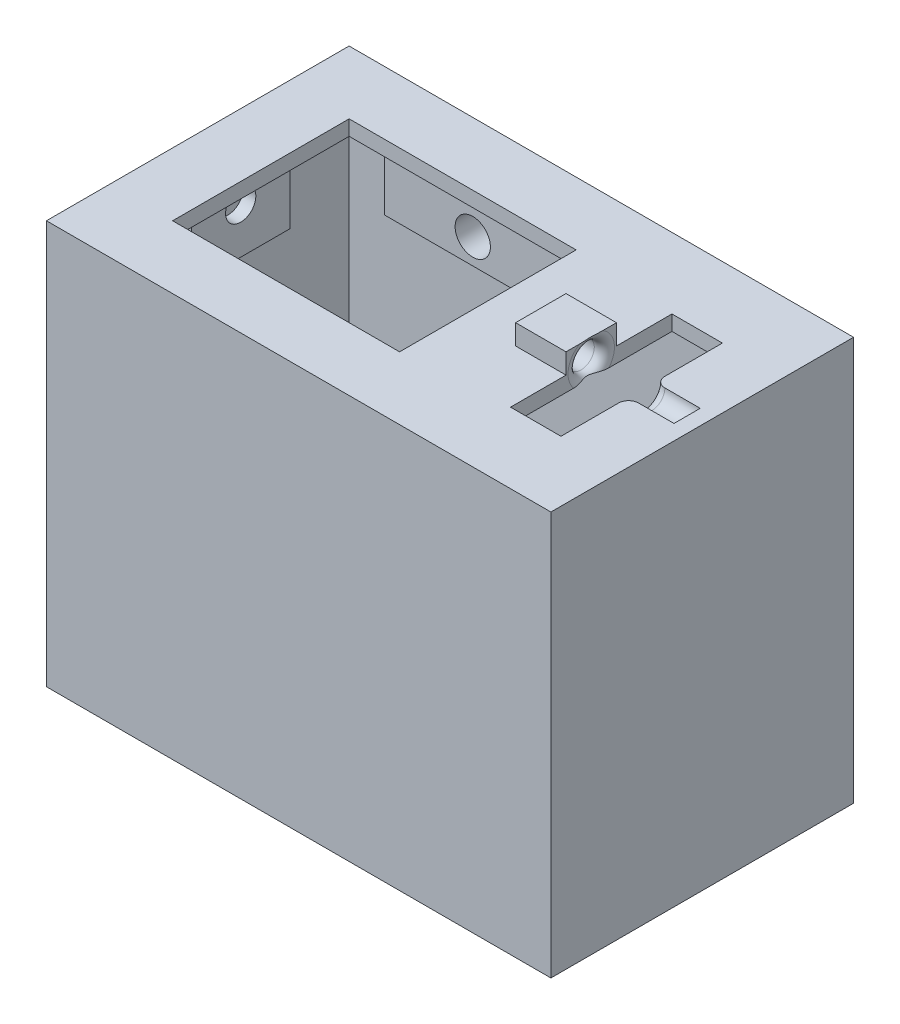
SolidWorks part; units mm, degrees
ref_plane "Front Plane" through (0, 0, 0) normal (0, 0, 1) x (1, 0, 0)
ref_plane "Top Plane" through (0, 0, 0) normal (0, 1, 0) x (1, 0, 0)
ref_plane "Right Plane" through (0, 0, 0) normal (1, 0, 0) x (0, 0, -1)
sketch "Sketch1" plane through (0, 0, 0) normal (0, 1, 0) x (1, 0, 0)
  line L1 (-63.5, -38.1) -> (63.5, -38.1)
  line L2 (-63.5, -38.1) -> (-63.5, 38.1)
  line L3 (-63.5, 38.1) -> (63.5, 38.1)
  line L4 (63.5, -38.1) -> (63.5, 38.1)
  line L5 (-63.5, -38.1) -> (63.5, 38.1) construction
  line L6 (-63.5, 38.1) -> (63.5, -38.1) construction
  point P0 (0, 0)
  dimension "D1" = 127
  dimension "D2" = 76.2
extrude "main body" add sketch "Sketch1" along normal blind 101.6
shell "hollow it" thickness 3.81 removed face at (0, 0, 0)
sketch "Sketch2" plane through (0, 101.6, 0) normal (0, 1, 0) x (1, 0, 0)
  line L0 (63.5, -38.1) -> (63.5, 38.1) construction
  line L1 (48.26, 20.32) -> (35.56, 20.32)
  line L2 (48.26, 20.32) -> (48.26, -20.32)
  line L3 (48.26, -20.32) -> (35.56, -20.32)
  line L4 (35.56, 20.32) -> (35.56, -20.32)
  line L5 (48.26, 20.32) -> (35.56, -20.32) construction
  line L6 (48.26, -20.32) -> (35.56, 20.32) construction
  point P0 (41.91, 0)
  dimension "D1" = 40.64
  dimension "D2" = 12.7
  dimension "D3" = 15.24
extrude "hole for scrollwheel" cut sketch "Sketch2" against normal up to next
ref_plane "arm guys plane" through (35.56, 0, 0) normal (1, 0, 0) x (0, 0, -1)
sketch "Sketch3" plane through (35.56, 0, 0) normal (1, 0, 0) x (0, 0, -1)
  line L0 (0, 101.6) -> (6.35, 101.6)
  line L1 (20.32, 101.6) -> (-20.32, 101.6) construction
  line L2 (6.35, 101.6) -> (6.35, 106.68)
  line L3 (6.35, 106.68) -> (-6.35, 106.68)
  line L4 (-6.35, 106.68) -> (-6.35, 101.6)
  line L5 (-6.35, 101.6) -> (0, 101.6)
  dimension "D1" = 6.35
  dimension "D2" = 6.35
  dimension "D3" = 5.08
extrude "nibble base hole" add sketch "Sketch3" against normal blind 12.7
ref_point "nibble base point"
sketch "Sketch5" plane through (35.56, 0, 0) normal (1, 0, 0) x (0, 0, -1)
  circle A0 centre (0, 101.6) radius 3.302
extrude "nibble hole" cut sketch "Sketch5" against normal blind 11.43 and the other way blind 24.13
fillet "easy to insert scroll wheel" radius 2.54 2 edges at (48.26, 98.298, 0) (35.56, 101.6, 3.302)
sketch "Sketch6" plane through (0, 101.6, 0) normal (0, 1, 0) x (1, 0, 0)
  line L1 (9.5368, 22.225) -> (-47.6132, 22.225)
  line L2 (9.5368, 22.225) -> (9.5368, -22.225)
  line L3 (9.5368, -22.225) -> (-47.6132, -22.225)
  line L4 (-47.6132, 22.225) -> (-47.6132, -22.225)
  line L5 (9.5368, 22.225) -> (-47.6132, -22.225) construction
  line L6 (9.5368, -22.225) -> (-47.6132, 22.225) construction
  point P0 (-19.0382, 0)
  dimension "D1" = 57.15
  dimension "D2" = 44.45
  dimension "D3" = 0
extrude "hole for joystick" cut sketch "Sketch6" against normal blind 11.43
sketch "Sketch10" plane through (0, 97.79, 0) normal (0, -1, 0) x (1, 0, 0)
  line L0 (-59.69, 34.29) -> (59.69, 34.29) construction
  line L1 (-41.2632, 31.75) -> (3.1868, 31.75)
  line L2 (-41.2632, 31.75) -> (-41.2632, 24.765)
  line L3 (-41.2632, 24.765) -> (3.1868, 24.765)
  line L4 (3.1868, 31.75) -> (3.1868, 24.765)
  line L5 (-41.2632, 31.75) -> (3.1868, 24.765) construction
  line L6 (-41.2632, 24.765) -> (3.1868, 31.75) construction
  line L7 (59.69, -34.29) -> (-59.69, -34.29) construction
  line L8 (-41.2632, -31.75) -> (3.1868, -31.75)
  line L9 (-41.2632, -31.75) -> (-41.2632, -24.765)
  line L10 (-41.2632, -24.765) -> (3.1868, -24.765)
  line L11 (3.1868, -31.75) -> (3.1868, -24.765)
  line L12 (-41.2632, -31.75) -> (3.1868, -24.765) construction
  line L13 (-41.2632, -24.765) -> (3.1868, -31.75) construction
  point P0 (-19.0382, 28.2575)
  point P5 (0, 34.29)
  point P10 (-19.0382, -28.2575)
  point P15 (0, -34.29)
  dimension "D1" = 6.35
  dimension "D2" = 6.35
  dimension "D3" = 2.54
  dimension "D4" = 2.54
  dimension "D5" = 2.54
  dimension "D6" = 2.54
  dimension "D7" = 44.45
  dimension "D8" = 0
extrude "box nibble base" add sketch "Sketch10" along normal blind 15.24
sketch "Sketch11" plane through (0, 97.79, 0) normal (0, -1, 0) x (1, 0, 0)
  line L0 (9.5368, -22.225) -> (9.5368, 22.225) construction
  line L1 (10.8068, -12.4282) -> (15.3788, -12.4282)
  line L2 (10.8068, -12.4282) -> (10.8068, 12.4282)
  line L3 (10.8068, 12.4282) -> (15.3788, 12.4282)
  line L4 (15.3788, -12.4282) -> (15.3788, 12.4282)
  line L5 (10.8068, -12.4282) -> (15.3788, 12.4282) construction
  line L6 (10.8068, 12.4282) -> (15.3788, -12.4282) construction
  line L7 (-47.6132, -22.225) -> (-47.6132, 22.225) construction
  line L8 (-55.88, -12.4282) -> (-52.6932, -12.4282)
  line L9 (-55.88, -12.4282) -> (-55.88, 12.4282)
  line L10 (-55.88, 12.4282) -> (-52.6932, 12.4282)
  line L11 (-52.6932, -12.4282) -> (-52.6932, 12.4282)
  line L12 (-55.88, -12.4282) -> (-52.6932, 12.4282) construction
  line L13 (-55.88, 12.4282) -> (-52.6932, -12.4282) construction
  line L14 (-59.69, -34.29) -> (-59.69, 34.29) construction
  point P0 (13.0928, 0)
  point P5 (9.5368, 0)
  point P8 (-54.2866, 0)
  point P14 (-47.6132, 0)
  point P17 (-59.69, 0)
  dimension "D1" = 1.27
  dimension "D2" = 4.572
  dimension "D3" = 5.08
  dimension "D4" = 3.81
  dimension "D5" = 3.1868
extrude "arch nibble base" add sketch "Sketch11" along normal blind 17.78
sketch "Sketch12" plane through (10.8068, 0, 0) normal (-1, 0, 0) x (0, 0, 1)
  line L1 (-22.225, 97.79) -> (22.225, 97.79) construction
  circle A0 centre (0, 91.44) radius 3.81
  dimension "D2" = 7.62
  dimension "D1" = 6.35
extrude "arch nibble holes" cut sketch "Sketch12" against normal up to surface and the other way up to surface up to face at (15.3788, 88.9, 0) other way up to face at (-59.69, 48.895, 0)
sketch "Sketch13" plane through (0, 0, -24.765) normal (0, 0, 1) x (1, 0, 0)
  line L0 (3.1868, 82.55) -> (3.1868, 97.79) construction
  line L1 (-41.2632, 82.55) -> (-41.2632, 97.79) construction
  line L2 (3.1868, 82.55) -> (-41.2632, 82.55) construction
  circle A0 centre (-19.0382, 88.9) radius 4.445
  point P2 (3.1868, 90.17)
  point P5 (-41.2632, 90.17)
  point P8 (-19.0382, 82.55)
  dimension "D3" = 8.89
  dimension "D1" = 22.225
  dimension "D2" = 22.225
  dimension "D4" = 6.35
extrude "box nibble holes" cut sketch "Sketch13" against normal up to surface and the other way up to surface up to face at (0, 48.895, -34.29) other way up to face at (0, 48.895, 34.29)
